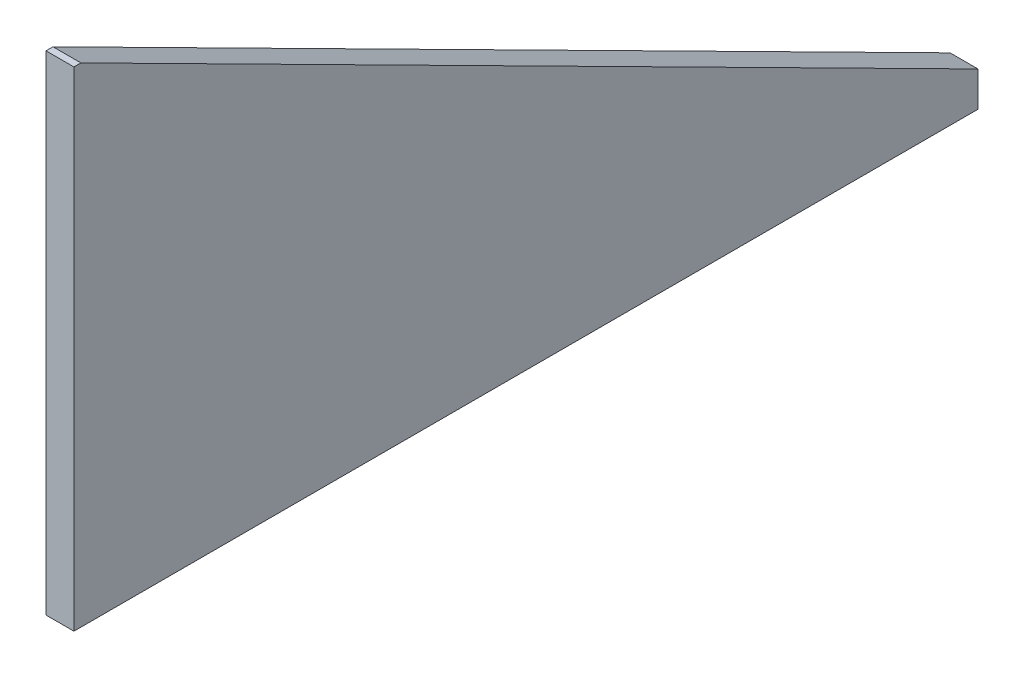
SolidWorks part; units mm, degrees
material "普通碳钢"
ref_plane "前视基准面" through (0, 0, 0) normal (0, 0, 1) x (1, 0, 0)
ref_plane "上视基准面" through (0, 0, 0) normal (0, 1, 0) x (1, 0, 0)
ref_plane "右视基准面" through (0, 0, 0) normal (1, 0, 0) x (0, 0, -1)
sketch "草图1" plane through (0, 0, 0) normal (1, 0, 0) x (0, 0, -1)
  line L0 (0, 0) -> (0, 280)
  line L1 (0, 280) -> (4, 280)
  line L2 (4, 280) -> (518, 20)
  line L3 (518, 20) -> (518, 0)
  line L4 (518, 0) -> (0, 0)
  dimension "D1" = 518
  dimension "D2" = 4
  dimension "D3" = 280
  dimension "D4" = 20
base flange "基体-法兰1" sketch "草图1" thickness 16 reverse thickness direction no parameters "D1"=10
sketch "草图6" plane through (0, 0, 0) normal (1, 0, 0) x (0, 0, -1)
  line L0 (4, 280) -> (0, 280) construction
  line L1 (0, 280) -> (518, 280)
  line L2 (0, 280) -> (0, 0)
  line L3 (0, 0) -> (518, 0)
  line L4 (518, 280) -> (518, 0)
  line L5 (0, 280) -> (0, 0) construction
  line L6 (0, 0) -> (518, 0) construction
  line L7 (518, 0) -> (518, 20) construction
  dimension "D1" = 518
  dimension "D2" = 280
sketch "折弯-线1" plane through (0, 0, 0) normal (0, 1, 0) x (1, 0, 0)
sketch "边界框1" plane through (0, 0, 0) normal (0, 1, 0) x (1, 0, 0)
sheet metal parameters "钣金1" thickness 16 parameters "D1"=10
flat pattern "平板型式1" [suppressed]
sketch "折弯-线2" plane through (0, 0, 0) normal (0, 1, 0) x (1, 0, 0)
sketch "边界框2" [suppressed] plane through (0, 0, 0) normal (0, 1, 0) x (1, 0, 0)
